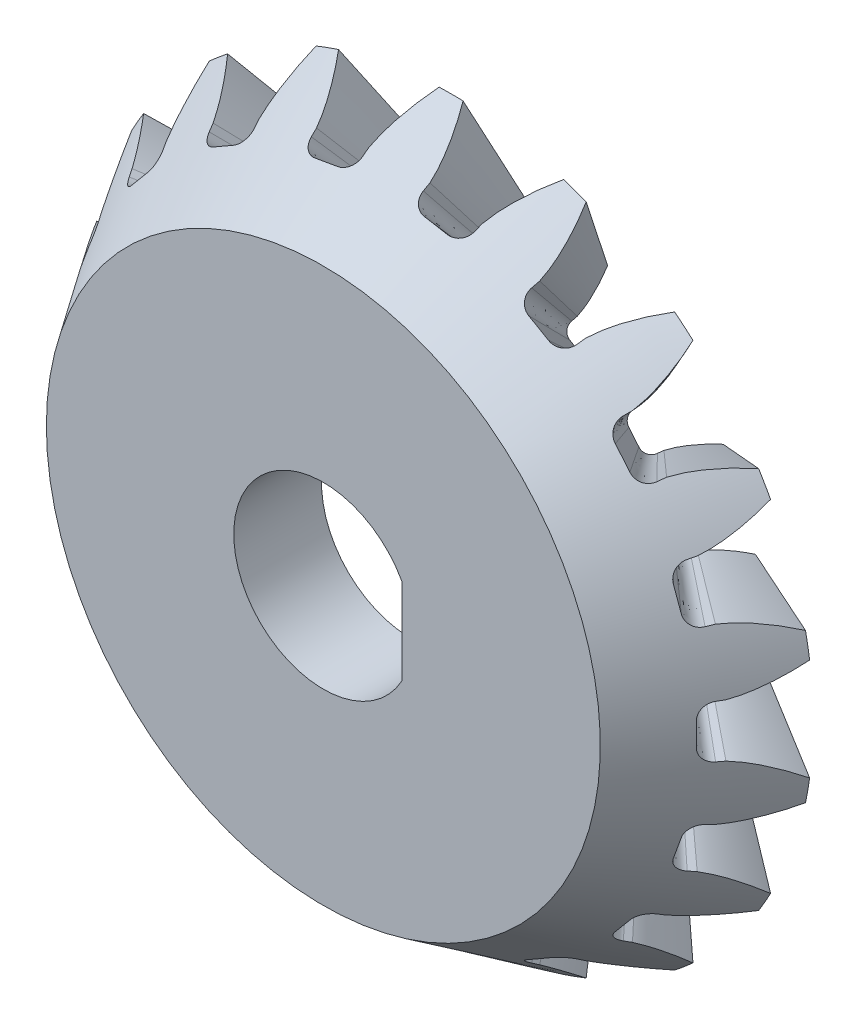
SolidWorks part; units mm, degrees
ref_plane "Front Plane" through (0, 0, 0) normal (0, 0, 1) x (1, 0, 0)
ref_plane "Top Plane" through (0, 0, 0) normal (0, 1, 0) x (1, 0, 0)
ref_plane "Right Plane" through (0, 0, 0) normal (1, 0, 0) x (0, 0, -1)
ref_axis "Gear Axis" through (0, 0, -0.9465) along (0, 0, 1)
sketch "Blank Sketch" plane through (0, 0, 0) normal (0, 1, 0) x (1, 0, 0)
  line L0 (0, 0) -> (0, -18.9291) construction
  line L1 (0, 0) -> (15.75, -10.5) construction
  line L2 (0, 0) -> (10.7577, -7.1718) construction
  line L3 (8.0506, -11.2325) -> (11.1934, -6.5182)
  line L4 (11.1934, -6.5182) -> (16.4727, -9.416)
  line L5 (16.4727, -9.416) -> (12.5987, -15.2269)
  line L6 (12.5987, -15.2269) -> (4.075, -15.2269)
  line L7 (4.075, -15.2269) -> (4.075, -11.2325)
  line L8 (4.075, -11.2325) -> (8.0506, -11.2325)
  line L9 (15.75, -10.5) -> (16.4727, -9.416) construction
  line L10 (15.75, -10.5) -> (12.5987, -15.2269) construction
  line L11 (10.7577, -7.1718) -> (8.0506, -11.2325) construction
  dimension "Axis" = 18.9291
  dimension "Cone" = 56.31
  dimension "Heel" = 18.9291
  dimension "Toe Cone" = 56.31
  dimension "Toe" = 12.9291
  dimension "Heel Square" = 90
  dimension "Addendum" = 1.3028
  dimension "Root Square" = 90
  dimension "Heel Rim" = 5.6811
  dimension "Toe Square" = 90
  dimension "Toe Rim" = 4.8803
  dimension "Front Square" = 90
  dimension "Face" = 4.927
  dimension "Back" = 8.5237
  dimension "Front" = 3.9756
revolve "Blank" add sketch "Blank Sketch" angle 360 about L0
sketch "Cone Sketch" plane through (0, 0, 0) normal (0, 1, 0) x (1, 0, 0)
  line L0 (0, 0) -> (0, -18.9291) construction
  line L1 (0, 0) -> (17.2061, -11.4707)
  line L2 (0, 0) -> (9.3016, -6.2011)
  dimension "Axis" = 18.9291
  dimension "Toe Cone" = 56.31
  dimension "Heel Cone" = 56.31
  dimension "Heel" = 20.6791
  dimension "Toe" = 11.1791
ref_plane "Heel Plane" through (17.2061, 0, 11.4707) normal (0.8321, 0, 0.5547) x (0.5547, 0, -0.8321)
ref_plane "Toe Plane" through (9.3016, 0, 6.2011) normal (0.8321, 0, 0.5547) x (0.5547, 0, -0.8321)
sketch "Heel Section Sketch" plane through (17.2061, 0, 11.4707) normal (0.8321, 0, 0.5547) x (0.5547, 0, -0.8321)
  line L0 (0, 0) -> (-31.0187, 0) construction
  line L1 (-1.6998, 1.3218) -> (-2.0718, 1.3051)
  line L2 (-1.6998, -1.3218) -> (-2.0718, -1.3051)
  line L3 (3.1252, 3.7908) -> (3.1252, -3.7908)
  arc A0 (-2.0718, 1.3051) -> (-2.7654, 0.5648) centre (-2.0391, 0.5793) ccw
  arc A1 (-2.7654, -0.5648) -> (-2.0718, -1.3051) centre (-2.0391, -0.5793) ccw
  arc A2 (-2.7654, -0.5648) -> (-2.7654, 0.5648) centre (-31.0187, 0) ccw
  spline S0 degree 4 poles (-1.835, 1.3029) (-1.8035, 1.3063) (-1.7265, 1.3172) (-1.6699, 1.3263) (-1.5187, 1.3548) (-1.4047, 1.3809) (-1.2491, 1.4187) (-1.0988, 1.4611) (-0.9327, 1.5108) (-0.7743, 1.5631) (-0.6131, 1.6193) (-0.4554, 1.6781) (-0.2911, 1.7425) (-0.0902, 1.8257) (0.1489, 1.931) (0.4216, 2.0595) (0.7251, 2.2137) (1.0206, 2.373) (1.3178, 2.5441) (1.6017, 2.7149) (1.8964, 2.9041) (2.1627, 3.0801) (2.4652, 3.2937) (2.6972, 3.4604) (3.0193, 3.7069) (3.1693, 3.8249) (3.3542, 3.9742) (3.4593, 4.0608) (3.5088, 4.1021) (3.5361, 4.1249) (3.5499, 4.1365) knots 0 0 0 0 0 0.022117 0.039787 0.058126 0.081614 0.109122 0.13663 0.164138 0.191645 0.219153 0.246661 0.274169 0.305931 0.360947 0.415962 0.470978 0.525993 0.581009 0.636024 0.69104 0.746055 0.801071 0.856086 0.911102 0.955551 0.977775 0.988888 1 1 1 1 1 construction
  spline S1 degree 4 poles (-1.6998, 1.3218) (-1.676, 1.3257) (-1.6289, 1.334) (-1.5187, 1.3548) (-1.4047, 1.3809) (-1.2491, 1.4187) (-1.0988, 1.4611) (-0.9327, 1.5108) (-0.7743, 1.5631) (-0.6131, 1.6193) (-0.4554, 1.6781) (-0.2911, 1.7425) (-0.0902, 1.8257) (0.1489, 1.931) (0.4216, 2.0595) (0.7251, 2.2137) (1.0206, 2.373) (1.3178, 2.5441) (1.6017, 2.7149) (1.8964, 2.9041) (2.1627, 3.0801) (2.4652, 3.2937) (2.6972, 3.4604) (2.951, 3.6546) (3.0662, 3.7442) (3.1252, 3.7908) knots 0.022117 0.022117 0.022117 0.022117 0.022117 0.039787 0.058126 0.081614 0.109122 0.13663 0.164138 0.191645 0.219153 0.246661 0.274169 0.305931 0.360947 0.415962 0.470978 0.525993 0.581009 0.636024 0.69104 0.746055 0.801071 0.856086 0.911102 0.911102 0.911102 0.911102 0.911102
  spline S2 degree 4 poles (-1.835, -1.3029) (-1.8035, -1.3063) (-1.7265, -1.3172) (-1.6699, -1.3263) (-1.5187, -1.3548) (-1.4047, -1.3809) (-1.2491, -1.4187) (-1.0988, -1.4611) (-0.9327, -1.5108) (-0.7743, -1.5631) (-0.6131, -1.6193) (-0.4554, -1.6781) (-0.2911, -1.7425) (-0.0902, -1.8257) (0.1489, -1.931) (0.4216, -2.0595) (0.7251, -2.2137) (1.0206, -2.373) (1.3178, -2.5441) (1.6017, -2.7149) (1.8964, -2.9041) (2.1627, -3.0801) (2.4652, -3.2937) (2.6972, -3.4604) (3.0193, -3.7069) (3.1693, -3.8249) (3.3542, -3.9742) (3.4593, -4.0608) (3.5088, -4.1021) (3.5361, -4.1249) (3.5499, -4.1365) knots 0 0 0 0 0 0.022117 0.039787 0.058126 0.081614 0.109122 0.13663 0.164138 0.191645 0.219153 0.246661 0.274169 0.305931 0.360947 0.415962 0.470978 0.525993 0.581009 0.636024 0.69104 0.746055 0.801071 0.856086 0.911102 0.955551 0.977775 0.988888 1 1 1 1 1 construction
  spline S3 degree 4 poles (-1.6998, -1.3218) (-1.676, -1.3257) (-1.6289, -1.334) (-1.5187, -1.3548) (-1.4047, -1.3809) (-1.2491, -1.4187) (-1.0988, -1.4611) (-0.9327, -1.5108) (-0.7743, -1.5631) (-0.6131, -1.6193) (-0.4554, -1.6781) (-0.2911, -1.7425) (-0.0902, -1.8257) (0.1489, -1.931) (0.4216, -2.0595) (0.7251, -2.2137) (1.0206, -2.373) (1.3178, -2.5441) (1.6017, -2.7149) (1.8964, -2.9041) (2.1627, -3.0801) (2.4652, -3.2937) (2.6972, -3.4604) (2.951, -3.6546) (3.0662, -3.7442) (3.1252, -3.7908) knots 0.022117 0.022117 0.022117 0.022117 0.022117 0.039787 0.058126 0.081614 0.109122 0.13663 0.164138 0.191645 0.219153 0.246661 0.274169 0.305931 0.360947 0.415962 0.470978 0.525993 0.581009 0.636024 0.69104 0.746055 0.801071 0.856086 0.911102 0.911102 0.911102 0.911102 0.911102
  dimension "Root" = 28.2589
  dimension "Fillet" = 0.7265
  dimension "Centre" = 31.0187
sketch "Toe Section Sketch" plane through (9.3016, 0, 6.2011) normal (0.8321, 0, 0.5547) x (0.5547, 0, -0.8321)
  line L0 (0, 0) -> (-16.7687, 0) construction
  line L1 (-0.9189, 0.7146) -> (-1.12, 0.7055)
  line L2 (-0.9189, -0.7146) -> (-1.12, -0.7055)
  line L3 (1.6895, 2.0493) -> (1.6895, -2.0493)
  arc A0 (-1.12, 0.7055) -> (-1.495, 0.3053) centre (-1.1023, 0.3132) ccw
  arc A1 (-1.495, -0.3053) -> (-1.12, -0.7055) centre (-1.1023, -0.3132) ccw
  arc A2 (-1.495, -0.3053) -> (-1.495, 0.3053) centre (-16.7687, 0) ccw
  spline S0 degree 4 poles (-0.9938, 0.704) (-0.972, 0.7067) (-0.9348, 0.7118) (-0.9013, 0.7173) (-0.8223, 0.7322) (-0.7582, 0.7467) (-0.6761, 0.7668) (-0.5935, 0.7899) (-0.5045, 0.8167) (-0.4184, 0.845) (-0.3316, 0.8754) (-0.2461, 0.9072) (-0.1574, 0.942) (-0.0487, 0.987) (0.0805, 1.0439) (0.228, 1.1134) (0.392, 1.1967) (0.5518, 1.2828) (0.7124, 1.3753) (0.8659, 1.4677) (1.0252, 1.5699) (1.1692, 1.6651) (1.3326, 1.7806) (1.4582, 1.8707) (1.6321, 2.0039) (1.7236, 2.0759) (1.8392, 2.1694) (1.8897, 2.2116) (1.9186, 2.2357) knots 0 0 0 0 0 0.022117 0.039787 0.058126 0.081614 0.109122 0.13663 0.164138 0.191645 0.219153 0.246661 0.274169 0.305931 0.360947 0.415962 0.470978 0.525993 0.581009 0.636024 0.69104 0.746055 0.801071 0.856086 0.911102 0.955551 1 1 1 1 1 construction
  spline S1 degree 4 poles (-0.9189, 0.7146) (-0.906, 0.7167) (-0.8799, 0.7213) (-0.8223, 0.7322) (-0.7582, 0.7467) (-0.6761, 0.7668) (-0.5935, 0.7899) (-0.5045, 0.8167) (-0.4184, 0.845) (-0.3316, 0.8754) (-0.2461, 0.9072) (-0.1574, 0.942) (-0.0487, 0.987) (0.0805, 1.0439) (0.228, 1.1134) (0.392, 1.1967) (0.5518, 1.2828) (0.7124, 1.3753) (0.8659, 1.4677) (1.0252, 1.5699) (1.1692, 1.6651) (1.3326, 1.7806) (1.4582, 1.8707) (1.5952, 1.9756) (1.6576, 2.0241) (1.6895, 2.0493) knots 0.022117 0.022117 0.022117 0.022117 0.022117 0.039787 0.058126 0.081614 0.109122 0.13663 0.164138 0.191645 0.219153 0.246661 0.274169 0.305931 0.360947 0.415962 0.470978 0.525993 0.581009 0.636024 0.69104 0.746055 0.801071 0.856086 0.911102 0.911102 0.911102 0.911102 0.911102
  spline S2 degree 4 poles (-0.9938, -0.704) (-0.972, -0.7067) (-0.9348, -0.7118) (-0.9013, -0.7173) (-0.8223, -0.7322) (-0.7582, -0.7467) (-0.6761, -0.7668) (-0.5935, -0.7899) (-0.5045, -0.8167) (-0.4184, -0.845) (-0.3316, -0.8754) (-0.2461, -0.9072) (-0.1574, -0.942) (-0.0487, -0.987) (0.0805, -1.0439) (0.228, -1.1134) (0.392, -1.1967) (0.5518, -1.2828) (0.7124, -1.3753) (0.8659, -1.4677) (1.0252, -1.5699) (1.1692, -1.6651) (1.3326, -1.7806) (1.4582, -1.8707) (1.6321, -2.0039) (1.7236, -2.0759) (1.8392, -2.1694) (1.8897, -2.2116) (1.9186, -2.2357) knots 0 0 0 0 0 0.022117 0.039787 0.058126 0.081614 0.109122 0.13663 0.164138 0.191645 0.219153 0.246661 0.274169 0.305931 0.360947 0.415962 0.470978 0.525993 0.581009 0.636024 0.69104 0.746055 0.801071 0.856086 0.911102 0.955551 1 1 1 1 1 construction
  spline S3 degree 4 poles (-0.9189, -0.7146) (-0.906, -0.7167) (-0.8799, -0.7213) (-0.8223, -0.7322) (-0.7582, -0.7467) (-0.6761, -0.7668) (-0.5935, -0.7899) (-0.5045, -0.8167) (-0.4184, -0.845) (-0.3316, -0.8754) (-0.2461, -0.9072) (-0.1574, -0.942) (-0.0487, -0.987) (0.0805, -1.0439) (0.228, -1.1134) (0.392, -1.1967) (0.5518, -1.2828) (0.7124, -1.3753) (0.8659, -1.4677) (1.0252, -1.5699) (1.1692, -1.6651) (1.3326, -1.7806) (1.4582, -1.8707) (1.5952, -1.9756) (1.6576, -2.0241) (1.6895, -2.0493) knots 0.022117 0.022117 0.022117 0.022117 0.022117 0.039787 0.058126 0.081614 0.109122 0.13663 0.164138 0.191645 0.219153 0.246661 0.274169 0.305931 0.360947 0.415962 0.470978 0.525993 0.581009 0.636024 0.69104 0.746055 0.801071 0.856086 0.911102 0.911102 0.911102 0.911102 0.911102
  dimension "Root" = 15.2768
  dimension "Fillet" = 0.3927
  dimension "Centre" = 16.7687
loft "Tooth Space" cut profiles "Heel Section Sketch", "Toe Section Sketch"
pattern_circular "Teeth" count 18 over 360 about axis through (0, 0, -0.9465) along (0, 0, 1) of "Tooth Space"
sketch "D-Flat Sketch" plane through (0, 0, 0) normal (0, 0, 1) x (1, 0, 0)
  line L0 (3.575, -2.3894) -> (3.575, 2.3894)
  arc A0 (3.575, -2.3894) -> (3.575, 2.3894) centre (0, 0) ccw
sketch "Sketch2" plane through (0, 0, 0) normal (0, 0, 1) x (1, 0, 0)
  line L0 (3.575, -2.3894) -> (3.575, 2.3894)
  arc A0 (3.575, -2.3894) -> (3.575, 2.3894) centre (0, 0) ccw
extrude "D-Flat" add sketch "Sketch2" along normal blind 3.9945 from offset 11.2325
equation "\"No. of Teeth\"= 18"
equation "\"Module\"= 1.75"
equation "\"Bore Diameter\"= 8.15"
equation "\"Pressure Angle\"= 20"
equation "\"Shaft Angle\"= 90"
equation "\"Mate Teeth\"= 12"
equation "\"Pitch Cone Angle\"= IIF ( ( \"Mate Teeth\" / \"No. of Teeth\" + cos ( \"Shaft Angle\" ) ) > 0 , atn ( sin ( \"Shaft Angle\" ) / ( \"Mate Teeth\" / \"No. of Teeth\" + cos ( \"Shaft Angle\" ) ) ) , 180 + atn ( sin ( \"Shaft Angle\" ) / ( \"Mate Teeth\" / \"No. of Teeth\" + cos ( \"Shaft Angle\" ) ) ) )"
equation "\"Mate Cone Angle\"= \"Shaft Angle\" - \"Pitch Cone Angle\""
equation "\"Addendum\"= IIF ( \"No. of Teeth\" >= \"Mate Teeth\" , 0.54 * \"Module\" + 0.46 * \"Module\" / ( ( \"No. of Teeth\" * cos ( \"Mate Cone Angle\" ) ) / ( \"Mate Teeth\" * cos ( \"Pitch Cone Angle\" ) ) ) , 2 * \"Module\" - ( 0.54 * \"Module\" + 0.46 * \"Module\" / ( ( \"Mate Teeth\" * cos ( \"Pitch Cone Angle\" ) ) / ( \"No. of Teeth\" * cos ( \"Mate Cone Angle\" ) ) ) ) )"
equation "\"Outer Diameter\"= \"No. of Teeth\" * \"Module\" + 2 * \"Addendum\" * cos ( \"Pitch Cone Angle\" )"
equation "\"Pitch Diameter\"= \"No. of Teeth\" * \"Module\""
equation "\"Backlash\"= IIF ( \"Module\" <= 1 , 0.3 * \"Module\" , 0.3 )"
equation "\"Arc Length\"= ( ( \"Module\" * pi ) / 2 + \"Backlash\" - 2 * ( \"Addendum\" - \"Module\" ) * tan ( \"Pressure Angle\" ) )"
equation "\"Fillet Radius\"= 0.38 * \"Module\""
equation "\"Mate Addendum\"= 2 * \"Module\" - \"Addendum\""
equation "\"Dedendum\"= 2.188 * \"Module\" - \"Addendum\""
equation "\"Tooth Depth\"= \"Addendum\" + \"Dedendum\""
equation "\"Mate Dedendum\"= 2.188 * \"Module\" - \"Mate Addendum\""
equation "\"Face Width\"= 6"
equation "\"Cone Distance\"= \"Pitch Diameter\" / ( 2 * sin ( \"Pitch Cone Angle\" ) )"
equation "\"Dedendum Angle\"= atn ( \"Dedendum\" / \"Cone Distance\" )"
equation "\"Mate Dedendum Angle\"= atn ( \"Mate Dedendum\" / \"Cone Distance\" )"
equation "\"Face Angle\"= \"Pitch Cone Angle\" + \"Mate Dedendum Angle\""
equation "\"Root Angle\"= \"Pitch Cone Angle\" - \"Dedendum Angle\""
equation "\"Overrun\"= \"Module\""
equation "\"Back Cone Pitch Diameter\"= \"Pitch Diameter\" / cos ( \"Pitch Cone Angle\" )"
equation "\"Back Cone Outer Diameter\"= \"Back Cone Pitch Diameter\" + 2 * \"Addendum\""
equation "\"Root Diameter\"= \"Back Cone Outer Diameter\" - 2 * \"Tooth Depth\""
equation "\"Base Diameter\"= \"Back Cone Pitch Diameter\" * cos ( \"Pressure Angle\" )"
equation "\"Base Radius\"= \"Base Diameter\" / 2"
equation "\"Tooth Thickness\"= \"Module\" * pi - \"Arc Length\""
equation "\"Half Space Angle\"= ( \"Arc Length\" / \"Back Cone Pitch Diameter\" ) * 180 / pi"
equation "\"Involute Fn\"= tan ( \"Pressure Angle\" ) - \"Pressure Angle\" * pi / 180"
equation "\"Flank Offset\"= \"Arc Length\" / \"Back Cone Pitch Diameter\" - \"Involute Fn\""
equation "\"Tip Cap Diameter\"= \"Back Cone Outer Diameter\" + 2 * \"Module\""
equation "\"Flank Start Diameter\"= IIF ( \"Base Diameter\" >= ( \"Root Diameter\" + 3 * \"Fillet Radius\" ) , \"Base Diameter\" , \"Root Diameter\" + 3 * \"Fillet Radius\" )"
equation "\"Involute t1\"= ( abs ( ( \"Flank Start Diameter\" / \"Base Diameter\" ) ^ 2 - 1 ) ) ^ 0.5"
equation "\"Involute t2\"= ( abs ( ( \"Tip Cap Diameter\" / \"Base Diameter\" ) ^ 2 - 1 ) ) ^ 0.5"
equation "\"Flank Arc Radius\"= ( \"Back Cone Pitch Diameter\" / 2 ) * sin ( \"Pressure Angle\" )"
equation "\"Flank Centre Angle\"= \"Half Space Angle\" + \"Pressure Angle\""
equation "\"Heel Distance\"= \"Cone Distance\" + \"Overrun\""
equation "\"Toe Distance\"= \"Cone Distance\" - \"Face Width\" - \"Overrun\""
equation "\"Heel Scale\"= \"Heel Distance\" / \"Cone Distance\""
equation "\"Toe Scale\"= \"Toe Distance\" / \"Cone Distance\""
equation "\"Heel Virtual Radius\"= \"Heel Distance\" * tan ( \"Pitch Cone Angle\" )"
equation "\"Toe Virtual Radius\"= \"Toe Distance\" * tan ( \"Pitch Cone Angle\" )"
equation "\"Axis@Blank Sketch\"= \"Cone Distance\""
equation "\"Cone@Blank Sketch\"= \"Pitch Cone Angle\""
equation "\"Heel@Blank Sketch\"= \"Cone Distance\""
equation "\"Toe Cone@Blank Sketch\"= \"Pitch Cone Angle\""
equation "\"Toe@Blank Sketch\"= \"Cone Distance\" - \"Face Width\""
equation "\"Addendum@Blank Sketch\"= \"Addendum\""
equation "\"Heel Rim@Blank Sketch\"= \"Dedendum\" + \"Module\" / cos ( \"Pitch Cone Angle\" )"
equation "\"Toe Rim@Blank Sketch\"= \"Dedendum\" - \"Face Width\" * tan ( \"Dedendum Angle\" ) + \"Module\" / cos ( \"Pitch Cone Angle\" )"
equation "\"Face@Blank Sketch\"= \"Mate Dedendum Angle\""
equation "\"Back@Blank Sketch\"= \"Cone Distance\" * sin ( \"Pitch Cone Angle\" ) - \"Dedendum\" * cos ( \"Pitch Cone Angle\" ) - \"Module\" - \"Bore Diameter\" / 2"
equation "\"Front@Blank Sketch\"= ( \"Cone Distance\" - \"Face Width\" ) * sin ( \"Pitch Cone Angle\" ) - ( \"Dedendum\" - \"Face Width\" * tan ( \"Dedendum Angle\" ) + \"Module\" / cos ( \"Pitch Cone Angle\" ) ) * cos ( \"Pitch Cone Angle\" ) - \"Bore Diameter\" / 2"
equation "\"Axis@Cone Sketch\"= \"Cone Distance\""
equation "\"Heel Cone@Cone Sketch\"= \"Pitch Cone Angle\""
equation "\"Heel@Cone Sketch\"= \"Heel Distance\""
equation "\"Toe Cone@Cone Sketch\"= \"Pitch Cone Angle\""
equation "\"Toe@Cone Sketch\"= \"Toe Distance\""
equation "\"Centre@Heel Section Sketch\"= \"Heel Virtual Radius\""
equation "\"Root@Heel Section Sketch\"= ( \"Root Diameter\" / 2 ) * \"Heel Scale\""
equation "\"Fillet@Heel Section Sketch\"= ( \"Fillet Radius\" ) * \"Heel Scale\""
equation "\"Centre@Toe Section Sketch\"= \"Toe Virtual Radius\""
equation "\"Root@Toe Section Sketch\"= ( \"Root Diameter\" / 2 ) * \"Toe Scale\""
equation "\"Fillet@Toe Section Sketch\"= ( \"Fillet Radius\" ) * \"Toe Scale\""
equation "\"Count@Teeth\"= \"No. of Teeth\""
